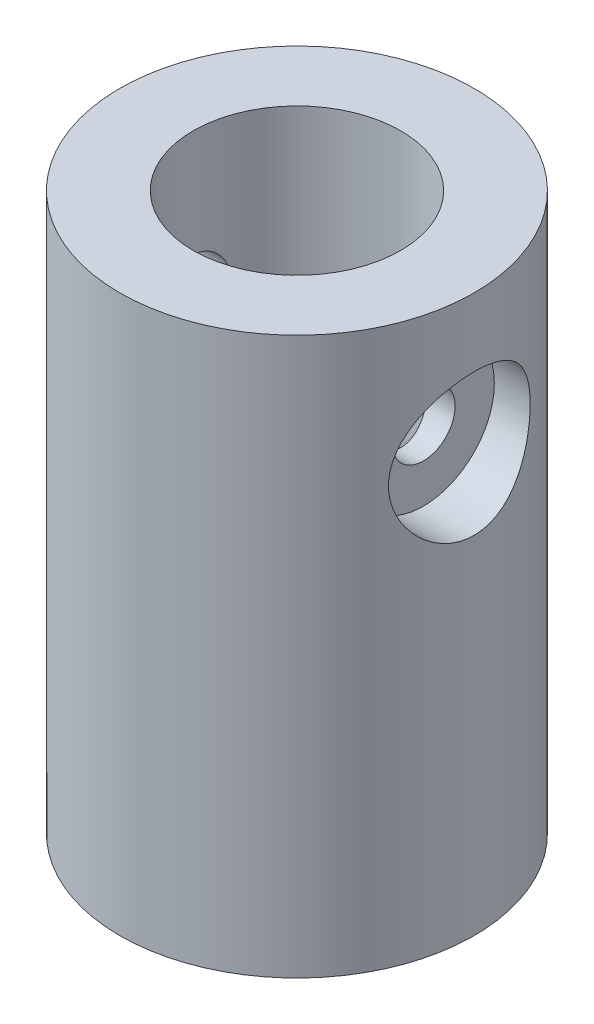
SolidWorks part; units mm, degrees
ref_plane "Front Plane" through (0, 0, 0) normal (0, 0, 1) x (1, 0, 0)
ref_plane "Top Plane" through (0, 0, 0) normal (0, 1, 0) x (1, 0, 0)
ref_plane "Right Plane" through (0, 0, 0) normal (1, 0, 0) x (0, 0, -1)
sketch "Sketch1" plane through (0, 0, 0) normal (0, 1, 0) x (1, 0, 0)
  circle A0 centre (0, 0) radius 7
  dimension "D1" = 14
extrude "Boss-Extrude1" add sketch "Sketch1" along normal blind 22 contours A0
sketch "Sketch2" plane through (0, 22, 0) normal (0, 1, 0) x (1, 0, 0)
  circle A0 centre (0, 0) radius 4.1
  dimension "D1" = 8.2
extrude "Cut-Extrude1" cut sketch "Sketch2" against normal blind 14 contours A0
sketch "Sketch3" plane through (0, 0, 0) normal (0, -1, 0) x (1, 0, 0)
  line L0 (-1.95, 2.0094) -> (-1.95, -2.0094)
  line L1 (1.95, 2.0094) -> (1.95, -2.0094)
  line L2 (0, 0) -> (0, 2.8) construction
  line L3 (0, 0) -> (0, -2.8) construction
  arc A0 (-1.95, -2.0094) -> (1.95, -2.0094) centre (0, 0) ccw
  arc A1 (1.95, 2.0094) -> (-1.95, 2.0094) centre (0, 0) ccw
  dimension "D1" = 5.6
  dimension "D2" = 1.95
  dimension "D3" = 1.95
extrude "Cut-Extrude2" cut sketch "Sketch3" against normal blind 8 contours L0 A0 L1 A1
hole_wizard "CBORE for M5 Hex Head Bolt1" positions "3DSketch1" profile "Sketch4" counterbore size "M5" standard "ANSI Metric" end condition through all
sketch3d "3DSketch1"
  line L0 (0, 22, 0) -> (0, 0, 0) construction
  line L1 (0, 22, 0) -> (0, 0, 0) construction
  line L2 (0, 16.5, 0) -> (7, 16.5, 0) construction
  point P0 (7, 16.5, 0)
  dimension "D1" = 5.5
sketch "Sketch4" plane through (7, 16.5, 0) normal (0, 1, 0) x (0, 0, -1)
  line L0 (0, 0) -> (0, 14)
  line L1 (0, 14) -> (1.25, 14)
  line L3 (1.25, 14) -> (1.25, 2)
  line L4 (1.25, 2) -> (2.8, 2)
  line L5 (2.8, 2) -> (2.8, 0)
  line L7 (2.8, 0) -> (0, 0)
  line L11 (0, -6.35) -> (0, 107.95) construction
  dimension "Thru Hole Dia." = 2.5
  dimension "Thru Hole Depth" = 14
  dimension "C'Bore Dia." = 5.6
  dimension "C'Bore Depth" = 2
